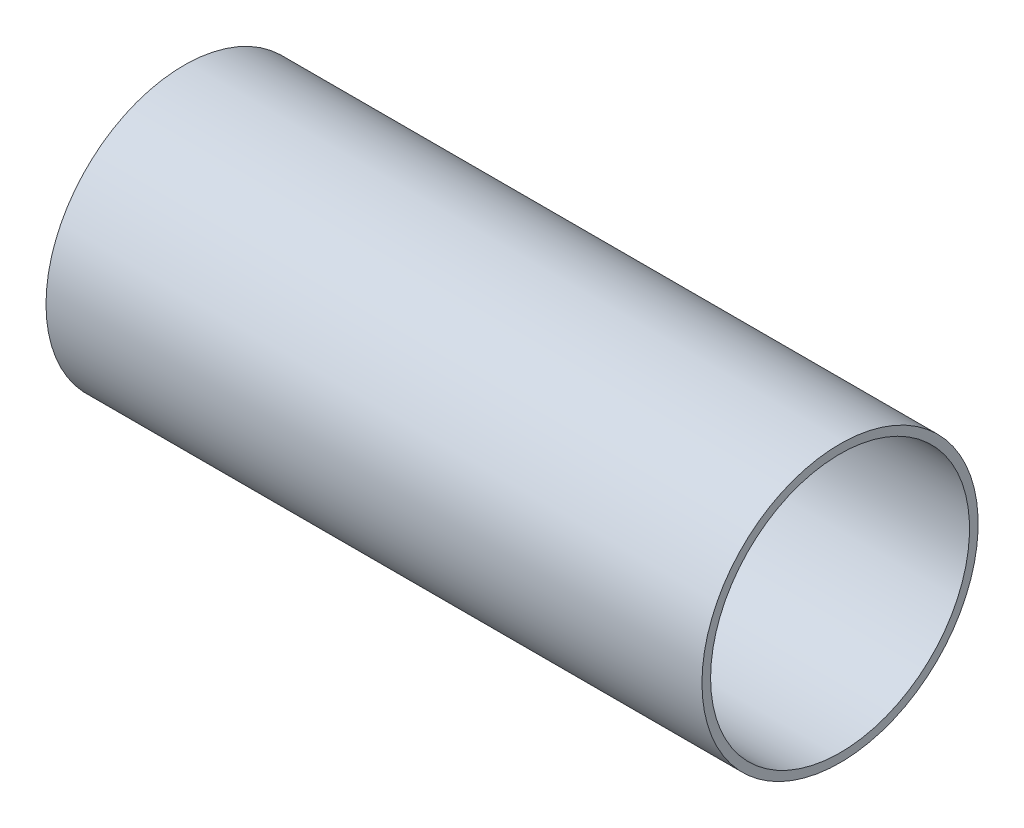
SolidWorks part; units mm, degrees
material "6061-T6 (SS)"
ref_plane "Front Plane" through (0, 0, 0) normal (0, 0, 1) x (1, 0, 0)
ref_plane "Top Plane" through (0, 0, 0) normal (0, 1, 0) x (1, 0, 0)
ref_plane "Right Plane" through (0, 0, 0) normal (1, 0, 0) x (0, 0, -1)
sketch "Sketch1" plane through (0, 0, 0) normal (1, 0, 0) x (0, 0, -1)
  circle A0 centre (0, 0) radius 101.6
  circle A1 centre (0, 0) radius 95.25
  dimension "D1" = 203.2
  dimension "D2" = 6.35
extrude "Boss-Extrude1" add sketch "Sketch1" along normal blind 482.6
